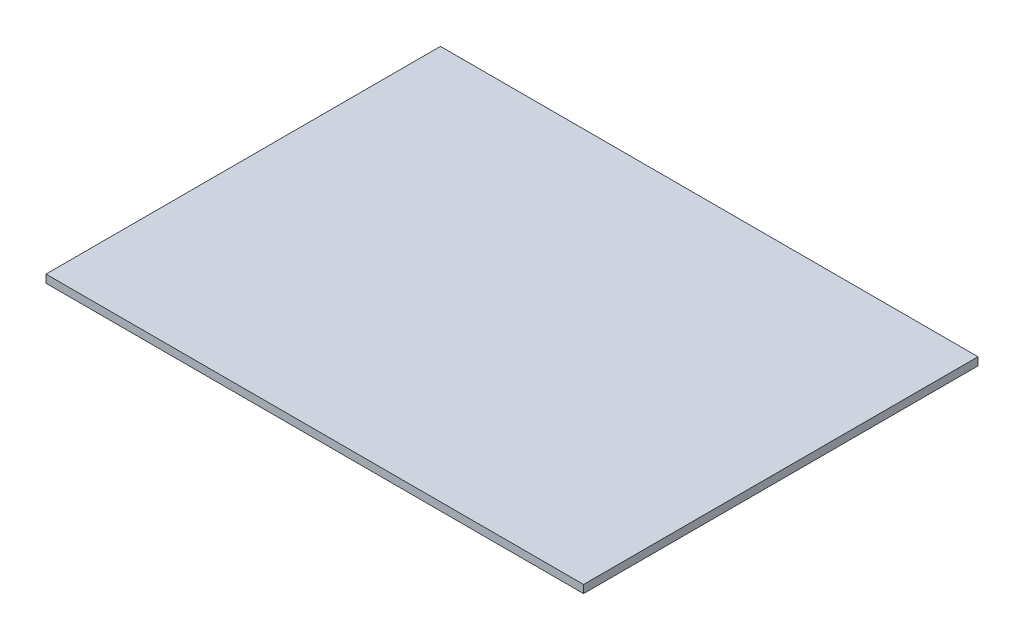
SolidWorks part; units mm, degrees
ref_plane "Front Plane" through (0, 0, 0) normal (0, 0, 1) x (1, 0, 0)
ref_plane "Top Plane" through (0, 0, 0) normal (0, 1, 0) x (1, 0, 0)
ref_plane "Right Plane" through (0, 0, 0) normal (1, 0, 0) x (0, 0, -1)
sketch "Sketch1" plane through (0, 0, 0) normal (0, 1, 0) x (1, 0, 0)
  line L1 (-169, -124) -> (169, -124)
  line L2 (-169, -124) -> (-169, 124)
  line L3 (-169, 124) -> (169, 124)
  line L4 (169, -124) -> (169, 124)
  line L5 (-169, -124) -> (169, 124) construction
  line L6 (-169, 124) -> (169, -124) construction
  point P0 (0, 0)
  dimension "D1" = 338
  dimension "D2" = 248
extrude "Boss-Extrude1" add sketch "Sketch1" along normal blind 5
